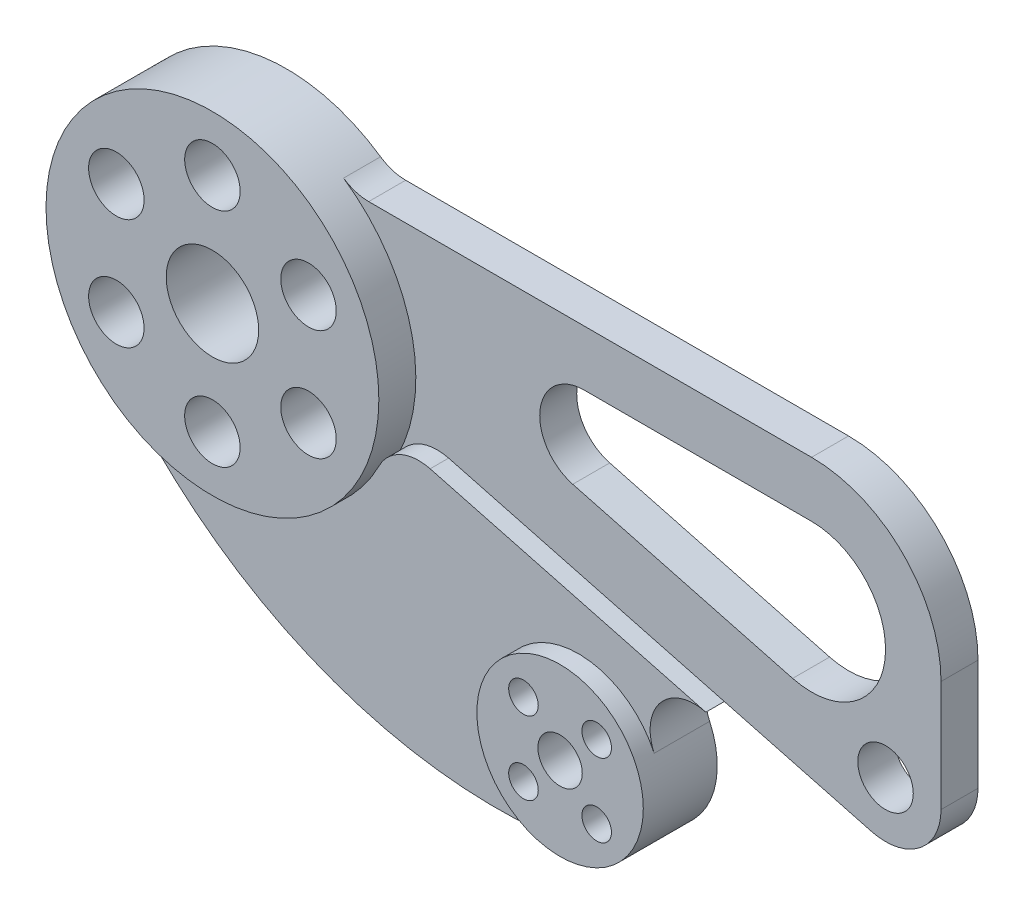
SolidWorks part; units mm, degrees
ref_plane "Спереди" through (0, 0, 0) normal (0, 0, 1) x (1, 0, 0)
ref_plane "Сверху" through (0, 0, 0) normal (0, 1, 0) x (1, 0, 0)
ref_plane "Справа" through (0, 0, 0) normal (1, 0, 0) x (0, 0, -1)
sketch "Эскиз5" plane through (0, 0, 0) normal (0, 0, 1) x (1, 0, 0)
  line L0 (0, 0) -> (405.866, 0) construction
  line L1 (0, 0) -> (-76.0744, 0) construction
  line L2 (0, 0) -> (0, 46.0865) construction
  line L3 (152, 0) -> (152, 104.1836) construction
  line L4 (152, 20) -> (90.4976, 20)
  line L5 (152, 35) -> (32.249, 35)
  line L6 (187, 0) -> (187, -30)
  line L7 (168.1626, -44.5009) -> (53.8683, -14.2552)
  line L8 (146.8835, -19.3345) -> (87.4277, -3.6007)
  line L9 (94, -82.5) -> (94, -37.5) construction
  line L10 (94, -60) -> (116.5, -60) construction
  line L11 (0, 0) -> (53.8683, -14.2552) construction
  circle A0 centre (0, 0) radius 45
  circle A1 centre (0, 30) radius 7.5
  circle A2 centre (25.9808, 15) radius 7.5
  circle A3 centre (25.9808, -15) radius 7.5
  circle A4 centre (0, -30) radius 7.5
  circle A5 centre (-25.9808, -15) radius 7.5
  circle A6 centre (-25.9808, 15) radius 7.5
  arc A7 (146.8835, -19.3345) -> (152, 20) centre (152, 0) ccw
  arc A8 (90.4976, 20) -> (87.4277, -3.6007) centre (90.4976, 8) ccw
  arc A9 (25.4598, 37.1053) -> (32.249, 35) centre (32.249, 47) ccw
  arc A10 (187, 0) -> (152, 35) centre (152, 0) ccw
  circle A11 centre (172, -30) radius 7.5
  arc A12 (168.1626, -44.5009) -> (187, -30) centre (172, -30) ccw
  arc A13 (53.8683, -14.2552) -> (40.104, -20.4125) centre (50.7984, -25.8558) ccw
  circle A14 centre (94, -60) radius 22.5
  circle A15 centre (0, 0) radius 12.5
  arc A16 (128.413, -33.9819) -> (114.4411, -50.5973) centre (125.3431, -45.5826) ccw
  arc A17 (-38.1037, -23.9396) -> (98.6101, -82.0226) centre (71.9737, 45.2193) ccw
  circle A18 centre (94, -60) radius 6
  circle A19 centre (84.1005, -69.8995) radius 4
  circle A20 centre (84.1005, -50.1005) radius 4
  circle A21 centre (103.8995, -50.1005) radius 4
  circle A22 centre (103.8995, -69.8995) radius 4
  point P20 (0, 0)
  point P62 (94, -60)
  dimension "D1" = 90
  dimension "D2" = 30
  dimension "D3" = 15
  dimension "D4" = 6
  dimension "D6" = 20
  dimension "D7" = 12
  dimension "D9" = 12
  dimension "D10" = 30
  dimension "D11" = 15
  dimension "D12" = 20
  dimension "D13" = 35
  dimension "D15" = 12
  dimension "D16" = 45
  dimension "D18" = 25
  dimension "D19" = 12
  dimension "D20" = 130
  dimension "D21" = 60
  dimension "D22" = 12
  dimension "D23" = 8
  dimension "D5" = 58
  dimension "D8" = 35
  dimension "D17" = 94
  dimension "D24" = 45
  dimension "D26" = 14
  dimension "D25" = 4
extrude "Бобышка-Вытянуть1" add sketch "Эскиз5" along normal blind 10 contours A13 L7 A12 L6 A10 L5 A9 A0 A11 A8 L4 A7 L8 region at (175.4674, 23.4674, 0)
extrude "Бобышка-Вытянуть2" add sketch "Эскиз5<3>" along normal blind 20 contours A0 A15 A6 A5 A4 A3 A2 A1 | A14 A22 A21 A20 A19 A18 region at (38.6902, 20.3749, 0) region at (74.4741, -50.1635, 0)
sketch "Эскиз5<3>" plane through (0, 0, 0) normal (0, 0, 1) x (1, 0, 0) same geometry as "Эскиз5"
extrude "Бобышка-Вытянуть3" add sketch "Эскиз5<4>" along normal blind 15 contours A0 A17 A14 A16 L7 A13 region at (48.7098, -49.5756, 0)
sketch "Эскиз5<4>" plane through (0, 0, 0) normal (0, 0, 1) x (1, 0, 0) same geometry as "Эскиз5"
